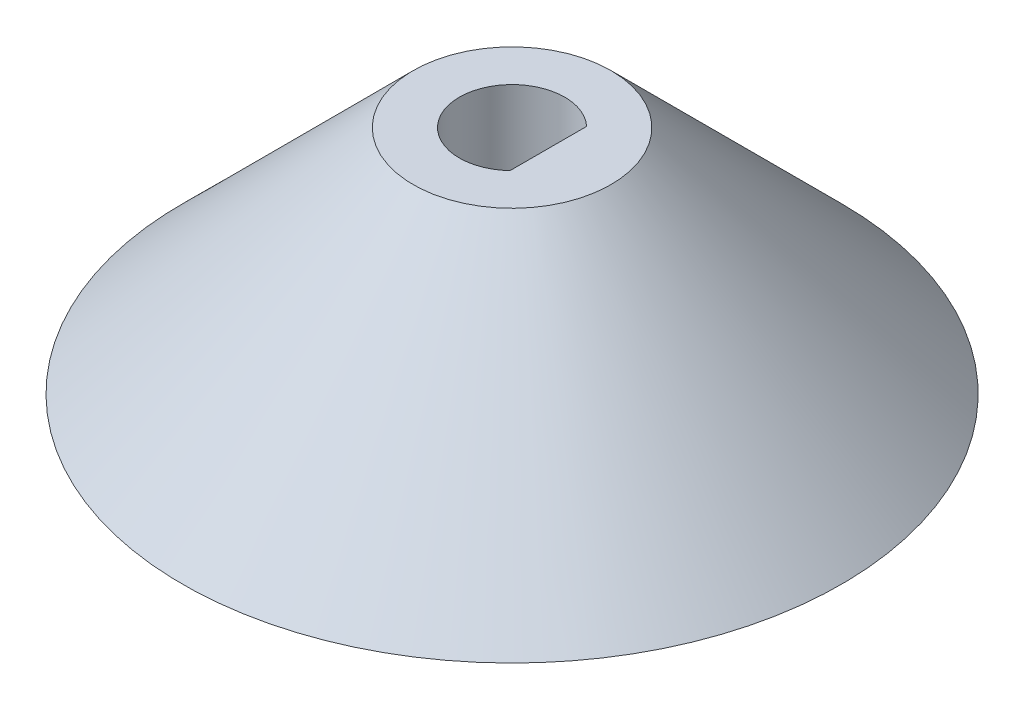
SolidWorks part; units mm, degrees
ref_plane "Front Plane" through (0, 0, 0) normal (0, 0, 1) x (1, 0, 0)
ref_plane "Top Plane" through (0, 0, 0) normal (0, 1, 0) x (1, 0, 0)
ref_plane "Right Plane" through (0, 0, 0) normal (1, 0, 0) x (0, 0, -1)
sketch "Sketch1" plane through (0, 0, 0) normal (0, 1, 0) x (1, 0, 0)
  circle A0 centre (0, 0) radius 10
extrude "Boss-Extrude1" add sketch "Sketch1" along normal blind 7
chamfer "Chamfer1" distance 7 angle 45 1 edges at (0, 7, 10)
sketch "Sketch2" plane through (0, 7, 0) normal (0, 1, 0) x (1, 0, 0)
  line L0 (1.1, 1.1619) -> (1.1, -1.1619)
  arc A0 (1.1, 1.1619) -> (1.1, -1.1619) centre (0, 0) ccw
  dimension "D1" = 3.2
  dimension "D2" = 1.1
extrude "Cut-Extrude1" cut sketch "Sketch2" against normal through all
sketch "Sketch5" plane through (0, 0, 0) normal (0, 0, 1) x (1, 0, 0)
  line L0 (0, 0) -> (0, 10) construction
sketch "Sketch6" plane through (0, 0, 0) normal (0, 0, 1) x (1, 0, 0)
  line L0 (10, 0) -> (0, 10) construction
sketch "Sketch9" plane through (0, 7, 0) normal (0, 1, 0) x (1, 0, 0)
  line L0 (0, 0) -> (0, -3) construction
  circle A0 centre (0, 0) radius 3 construction
ref_plane "Plane1" through (0, 0, 0) normal (0, 0, 1) x (1, 0, 0)
